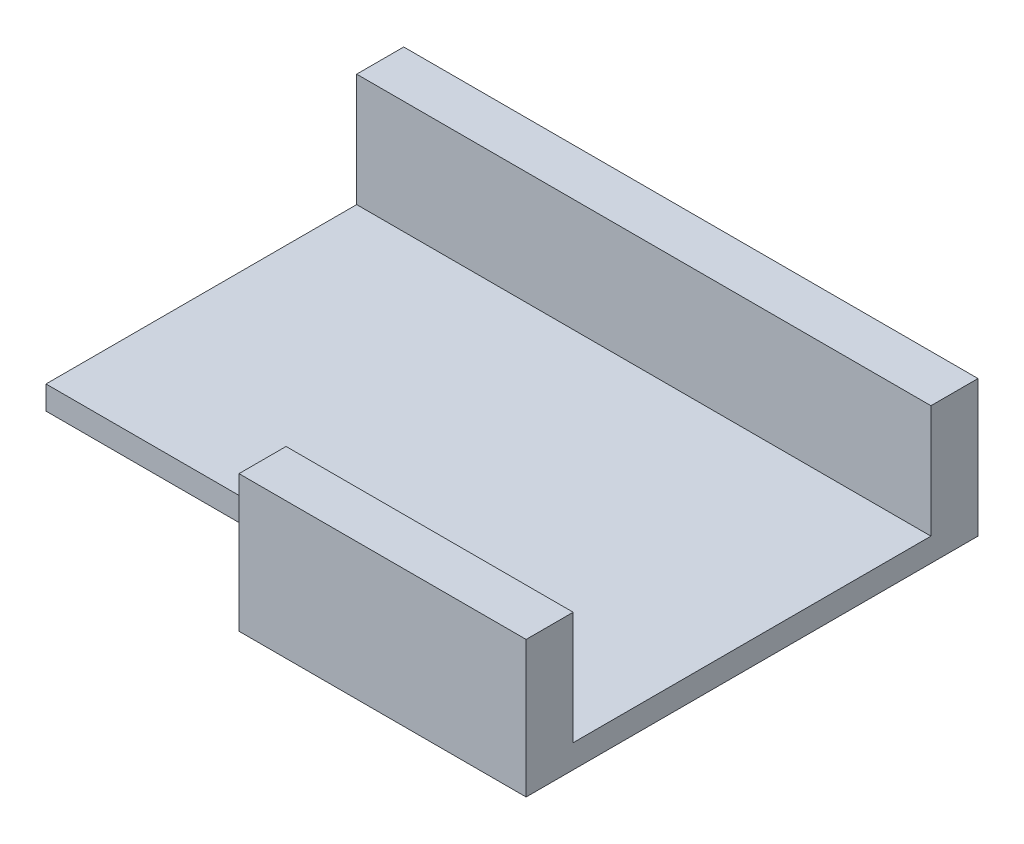
SolidWorks part; units mm, degrees
ref_plane "Front Plane" through (0, 0, 0) normal (0, 0, 1) x (1, 0, 0)
ref_plane "Top Plane" through (0, 0, 0) normal (0, 1, 0) x (1, 0, 0)
ref_plane "Right Plane" through (0, 0, 0) normal (1, 0, 0) x (0, 0, -1)
sketch "Sketch1" plane through (0, 0, 0) normal (0, 1, 0) x (1, 0, 0)
  line L0 (0, 10) -> (30.5, 10)
  line L3 (0, 48) -> (61, 48)
  line L4 (61, 0) -> (61, 48)
  line L5 (30.5, 10) -> (30.5, 0)
  line L6 (0, 48) -> (0, 10)
  line L7 (30.5, 0) -> (61, 0)
  dimension "D1" = 61
  dimension "D2" = 48
  dimension "D3" = 30.5
  dimension "D4" = 10
extrude "Boss-Extrude1" add sketch "Sketch1" along normal blind 2.5
sketch "Sketch2" plane through (0, 2.5, 0) normal (0, 1, 0) x (1, 0, 0)
  line L24 (61, 0) -> (61, 48) construction
  line L25 (0, 48) -> (61, 48)
  line L26 (0, 48) -> (0, 43)
  line L27 (0, 43) -> (61, 43)
  line L28 (61, 48) -> (61, 43)
  line L30 (30.5, 0) -> (61, 0)
  line L31 (30.5, 0) -> (30.5, 5)
  line L32 (30.5, 5) -> (61, 5)
  line L33 (61, 0) -> (61, 5)
  dimension "D1" = 5
  dimension "D2" = 5
extrude "Boss-Extrude2" add sketch "Sketch2" along normal blind 12
sketch "Sketch3" plane through (0, 0, 0) normal (0, -1, 0) x (1, 0, 0)
  line L0 (61, -24) -> (0, -24) construction
  line L1 (61, 0) -> (61, -48) construction
  line L2 (0, -48) -> (0, -10) construction
  text T0 "PCB" font "Arial Rounded MT Bold" height 3.5
extrude "Cut-Extrude1" cut sketch "Sketch3" against normal blind 1
